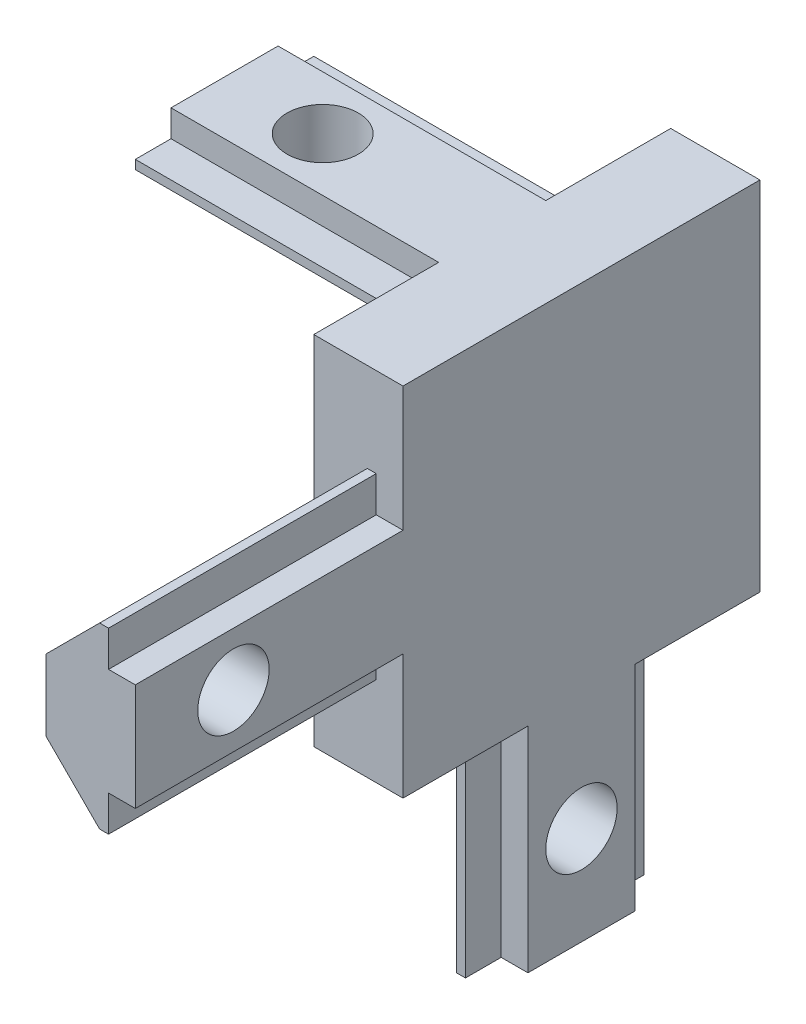
SolidWorks part; units mm, degrees
ref_plane "Front Plane" through (0, 0, 0) normal (0, 0, 1) x (1, 0, 0)
ref_plane "Top Plane" through (0, 0, 0) normal (0, 1, 0) x (1, 0, 0)
ref_plane "Right Plane" through (0, 0, 0) normal (1, 0, 0) x (0, 0, -1)
sketch "Sketch1" plane through (0, 0, 0) normal (1, 0, 0) x (0, 0, -1)
  line L0 (13, 11.9765) -> (13, 0)
  line L1 (0, 31.9765) -> (0, 11.9765) construction
  line L2 (0, 11.9765) -> (20, 11.9765) construction
  line L3 (20, 11.9765) -> (20, 31.9765) construction
  line L4 (10, 0) -> (10, 11.9765) construction
  line L5 (0, 24.9765) -> (-15, 24.9765)
  line L6 (-15, 24.9765) -> (-15, 18.9765)
  line L7 (-15, 18.9765) -> (0, 18.9765)
  line L8 (0, 11.9765) -> (0, 31.9765)
  line L9 (0, 31.9765) -> (20, 31.9765)
  line L10 (20, 31.9765) -> (20, 11.9765)
  line L11 (20, 11.9765) -> (0, 11.9765)
  line L12 (13, 0) -> (7, 0)
  line L13 (7, 0) -> (7, 11.9765)
  line L15 (-15, 21.9765) -> (0, 21.9765) construction
  circle A0 centre (10, 5.5) radius 2
  circle A1 centre (-9.5, 21.9765) radius 2
  dimension "D9" = 4
  dimension "D1" = 20
  dimension "D2" = 7
  dimension "D3" = 6
  dimension "D4" = 6
  dimension "D5" = 15
  dimension "D6" = 7
  dimension "D7" = 5.5
  dimension "D8" = 5.5
extrude "Boss-Extrude2" add sketch "Sketch1" along normal blind 1.5 contours L11 L10 L9 L8 | L7 L8 L5 L6 A1 | L13 L12 L0 L11 A0 region at (0, 21.9765, -10) region at (0, 5.9882, -12.866) region at (0, 21.9765, 7.1754)
sketch "Sketch2" plane through (0, 0, 0) normal (-1, 0, 0) x (0, 0, 1)
  line L0 (-20, 31.9765) -> (0, 31.9765)
  line L1 (0, 31.9765) -> (0, 24.9765)
  line L2 (0, 24.9765) -> (0, 11.9765)
  line L3 (0, 11.9765) -> (-20, 11.9765)
  line L4 (-20, 11.9765) -> (-20, 31.9765)
extrude "Boss-Extrude3" add sketch "Sketch2" along normal blind 3.5 contours L4 L0 L1 L2 L3
sketch "Sketch3" plane through (0, 0, 0) normal (-1, 0, 0) x (0, 0, 1)
  line L0 (-15, 0) -> (-5, 0)
  line L1 (-5, 0) -> (-5, 11.9765)
  line L2 (0, 11.9765) -> (-20, 11.9765) construction
  line L3 (-5, 11.9765) -> (-15, 11.9765)
  line L4 (-15, 11.9765) -> (-15, 0)
  line L5 (0, 16.9765) -> (15, 16.9765)
  line L6 (0, 31.9765) -> (0, 11.9765) construction
  line L8 (15, 26.9765) -> (0, 26.9765)
  line L9 (0, 26.9765) -> (0, 16.9765)
  line L10 (-20, 11.9765) -> (-20, 31.9765) construction
  line L11 (15, 16.9765) -> (15, 26.9765)
  dimension "D1" = 5
  dimension "D2" = 5
  dimension "D3" = 15
  dimension "D4" = 10
  dimension "D5" = 5
extrude "Boss-Extrude4" add sketch "Sketch3" along normal blind 3.5
sketch "Sketch5" plane through (0, 0, 0) normal (1, 0, 0) x (0, 0, -1)
  circle A0 centre (-9.5, 21.9765) radius 2
  circle A1 centre (10, 5.5) radius 2
extrude "Cut-Extrude1" cut sketch "Sketch5" against normal through all both and the other way through all
sketch "Sketch6" plane through (-3.5, 0, 0) normal (-1, 0, 0) x (0, 0, 1)
  line L0 (-10, 31.9765) -> (-10, 19.1517) construction
  line L1 (-20, 31.9765) -> (0, 31.9765) construction
  line L2 (-20, 21.9765) -> (3.4345, 21.9765) construction
  line L3 (-20, 11.9765) -> (-20, 31.9765) construction
  line L4 (-5, 31.9765) -> (-5, 29.9765)
  line L5 (-8, 26.9765) -> (-12, 26.9765)
  line L6 (-15, 29.9765) -> (-15, 31.9765)
  line L7 (-15, 31.9765) -> (-5, 31.9765)
  line L8 (-13, 31.9765) -> (-13, 30.4765)
  line L9 (-13, 30.4765) -> (-7, 30.4765)
  line L10 (-7, 30.4765) -> (-7, 31.9765)
  line L11 (-13, 30.4765) -> (-13, 31.9765)
  line L12 (-7, 31.9765) -> (-7, 30.4765)
  line L13 (-5, 26.9765) -> (-5, 31.9765)
  line L14 (-15, 31.9765) -> (-15, 26.9765)
  line L15 (-20, 24.9765) -> (-18.5, 24.9765)
  line L16 (-18.5, 24.9765) -> (-18.5, 18.9765)
  line L17 (-18.5, 18.9765) -> (-20, 18.9765)
  line L18 (-20, 18.9765) -> (-20, 24.9765)
  line L19 (-20, 26.9765) -> (-18, 26.9765)
  line L20 (-15, 23.9765) -> (-15, 19.9765)
  line L21 (-18, 16.9765) -> (-20, 16.9765)
  line L22 (-18.5, 26.9765) -> (-18.5, 16.9765)
  line L23 (-15, 30.4765) -> (-5, 30.4765)
  line L24 (-12, 26.9765) -> (-15, 29.9765)
  line L25 (-5, 29.9765) -> (-8, 26.9765)
  line L26 (-18, 26.9765) -> (-15, 23.9765)
  line L27 (-15, 19.9765) -> (-18, 16.9765)
  point P28 (-15, 26.9765)
  point P30 (-15, 26.9765)
  point P34 (-15, 16.9765)
  point P36 (-15, 16.9765)
  line M19 (-20, 31.9765) -> (-20, 11.9765)
  dimension "D1" = 5
  dimension "D2" = 10
  dimension "D3" = 6
  dimension "D4" = 1.5
  dimension "D5" = 10
  dimension "D6" = 6
  dimension "D7" = 5
  dimension "D8" = 1.5
extrude "Boss-Extrude6" add sketch "Sketch6" along normal blind 15 contours L27 L20 L26 L19 L22 L16 L21 | L17 L16 L15 M19 | L25 L13 L23 L9 L6 L24 L5 | L9 L10 L7 L8 region at (-3.5, 28.9861, -10) region at (-3.5, 31.2265, -10) region at (-3.5, 21.9765, -19.25) region at (-3.5, 21.9765, -17.0096)
chamfer "Chamfer1" distance 3 4 edges at (-3.5, 16.9765, 7.5) (-3.5, 26.9765, 7.5) (-3.5, 5.9882, -15) (-3.5, 5.9882, -5)
sketch "Sketch7" plane through (0, 31.9765, 0) normal (0, 1, 0) x (1, 0, 0)
  line L0 (-18.5, 10) -> (-13, 10) construction
  line L3 (-18.5, 7) -> (-18.5, 13) construction
  circle A1 centre (-13, 10) radius 2
  dimension "D1" = 4
  dimension "D2" = 5.5
sketch "Sketch8" plane through (0, 0, -20) normal (0, 0, -1) x (-1, 0, 0)
  line L0 (18.5, 21.9765) -> (13, 21.9765) construction
  line L2 (18.5, 24.9765) -> (18.5, 18.9765) construction
  circle A1 centre (13, 21.9765) radius 2
  dimension "D1" = 4
  dimension "D2" = 5.5
extrude "Cut-Extrude4" cut sketch "Sketch7" against normal through all both and the other way through all
extrude "Cut-Extrude5" cut sketch "Sketch8" against normal through all both and the other way through all contours A1
